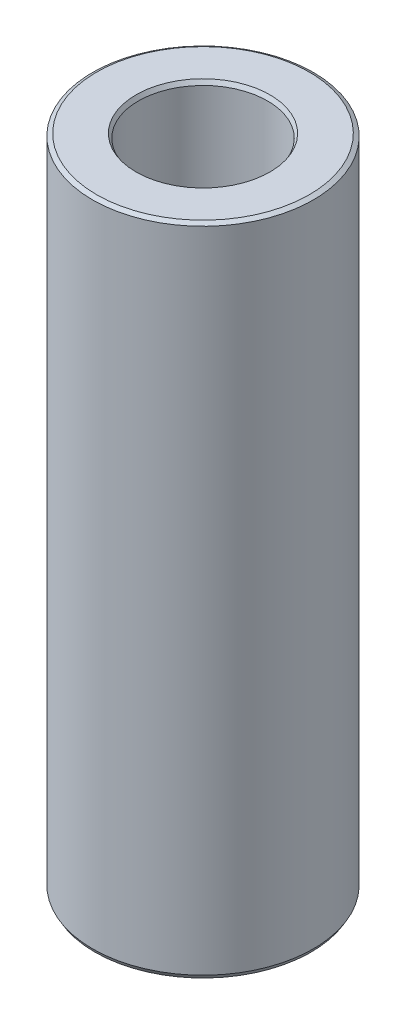
SolidWorks part; units mm, degrees
ref_plane "Front Plane" through (0, 0, 0) normal (0, 0, 1) x (1, 0, 0)
ref_plane "Top Plane" through (0, 0, 0) normal (0, 1, 0) x (1, 0, 0)
ref_plane "Right Plane" through (0, 0, 0) normal (1, 0, 0) x (0, 0, -1)
sketch "Sketch1" plane through (0, 0, 0) normal (0, 1, 0) x (1, 0, 0)
  circle A0 centre (0, 0) radius 45
  dimension "SLEEVE_OD" = 90
extrude "Boss-Extrude1" add sketch "Sketch1" along normal blind 266.9514
sketch "Sketch2" plane through (0, 0, 0) normal (0, 1, 0) x (1, 0, 0)
  circle A0 centre (0, 0) radius 26.3064
  dimension "BORE_D" = 52.6129
extrude "Cut-Extrude1" cut sketch "Sketch2" along normal through all
chamfer "Chamfer1" distance 0.97 angle 60 4 edges at (0, 266.9514, 26.3064) (0, 0, 26.3064) (0, 0, 45) (0, 266.9514, 45) first distance on face at (0, 266.9514, 26.3064) first distance on face at (0, 0, 26.3064) first distance on face at (0, 266.9514, 45)
